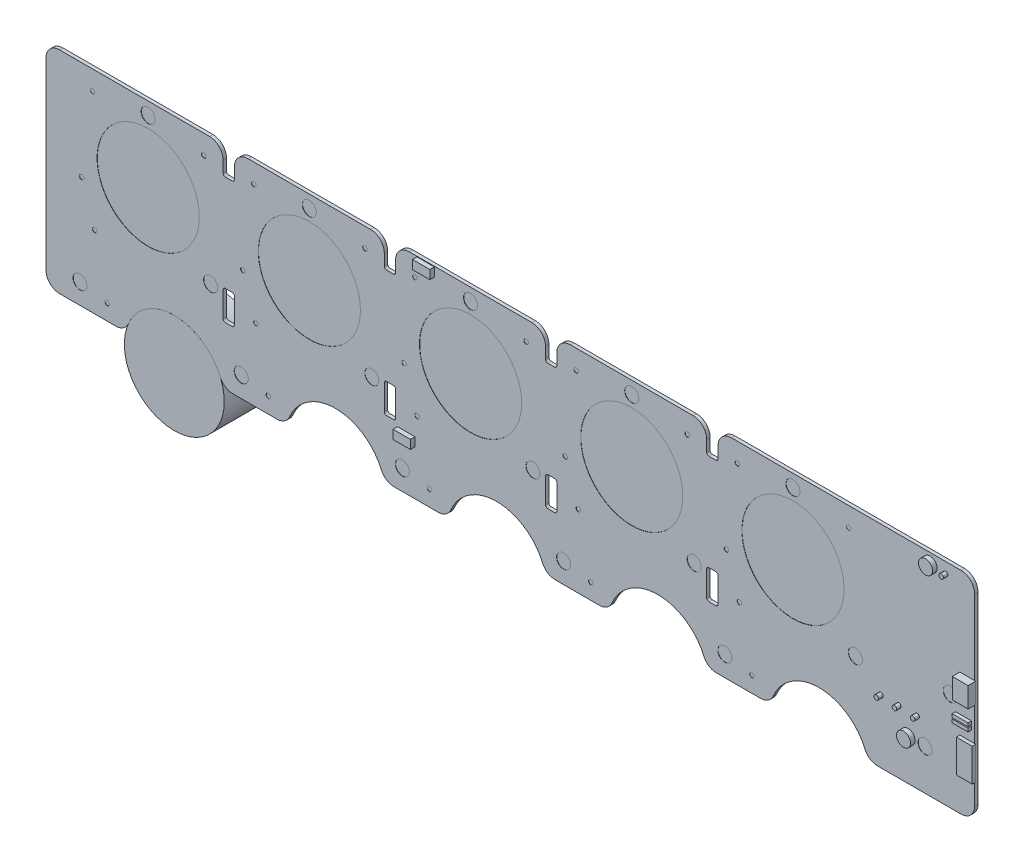
SolidWorks part; units mm, degrees
ref_plane "Plan de face" through (0, 0, 0) normal (0, 0, 1) x (1, 0, 0)
ref_plane "Plan de dessus" through (0, 0, 0) normal (0, 1, 0) x (1, 0, 0)
ref_plane "Plan de droite" through (0, 0, 0) normal (1, 0, 0) x (0, 0, -1)
sketch "Esquisse1" plane through (0, 0, 0) normal (0, 0, 1) x (1, 0, 0)
  line L0 (-142, 0) -> (-71, 0) construction
  line L1 (-187, 33) -> (222, 33)
  line L2 (-187, 33) -> (-187, -60)
  line L3 (-187, -60) -> (222, -60)
  line L4 (222, 33) -> (222, -60)
  line L5 (-71, 0) -> (0, 0) construction
  line L6 (0, 0) -> (71, 0) construction
  line L7 (71, 0) -> (142, 0) construction
  line L8 (-142, 0) -> (-187, 0) construction
  line L9 (142, 0) -> (222, 0) construction
  circle A0 centre (-142, 0) radius 22.5
  circle A1 centre (-71, 0) radius 22.5
  circle A2 centre (0, 0) radius 22.5
  circle A3 centre (71, 0) radius 22.5
  circle A4 centre (142, 0) radius 22.5
  dimension "D1" = 71
  dimension "D2" = 45
  dimension "D3" = 45
  dimension "D4" = 33
  dimension "D5" = 60
  dimension "D6" = 80
  dimension "D7" = 409
extrude "PCB_rectangulaire" add sketch "Esquisse1" against normal blind 1.5 contours L1 L4 L3 L2
extrude "position_trou" cut sketch "Esquisse1<3>" against normal blind 0.1 contours A0 | A1 | A2 | A3 | A4 region at (-142, 0, 0) region at (-71, 0, 0) region at (0, 0, 0) region at (71, 0, 0)
sketch "Esquisse1<3>" plane through (0, 0, 0) normal (0, 0, 1) x (1, 0, 0) same geometry as "Esquisse1"
sketch "Esquisse3" plane through (0, 0, 0) normal (0, 0, 1) x (1, 0, 0)
  line L0 (-187, 33) -> (222, 33) construction
  line L1 (-109, 33) -> (-104, 33)
  line L2 (-109, 33) -> (-109, 22)
  line L3 (-108, 21) -> (-105, 21)
  line L4 (-104, 33) -> (-104, 22)
  line L5 (-106.5, 21) -> (-106.5, 0) construction
  line L6 (-108, -21.5) -> (-105, -21.5)
  line L7 (-109, -22.5) -> (-109, -33.5)
  line L8 (-108, -34.5) -> (-105, -34.5)
  line L9 (-104, -22.5) -> (-104, -33.5)
  line L10 (-106.5, 0) -> (-106.5, -21.5) construction
  line L11 (-142, 0) -> (-71, 0) construction
  arc A0 (-105, 21) -> (-104, 22) centre (-105, 22) ccw
  arc A1 (-109, 22) -> (-108, 21) centre (-108, 22) ccw
  arc A2 (-105, -34.5) -> (-104, -33.5) centre (-105, -33.5) ccw
  arc A3 (-109, -33.5) -> (-108, -34.5) centre (-108, -33.5) ccw
  arc A4 (-105, -21.5) -> (-104, -22.5) centre (-105, -22.5) cw
  arc A5 (-108, -21.5) -> (-109, -22.5) centre (-108, -22.5) ccw
  point P17 (-104, -28)
  point P20 (-104, 21)
  point P25 (-104, -34.5)
  point P28 (-109, -34.5)
  point P31 (-104, -21.5)
  dimension "D5" = 1
  dimension "D1" = 5
  dimension "D2" = 12
  dimension "D3" = 13
  dimension "D4" = 28
extrude "passage_appui_flanc et passage jeton" cut sketch "Esquisse3" against normal through all
pattern_linear "Répétition linéaire1" count 4 spacing 71 along (1, 0, 0) of "passage_appui_flanc et passage jeton"
sketch "Esquisse2" plane through (0, 0, 0) normal (0, 0, 1) x (1, 0, 0)
  line L6 (-166.4921, 24.4921) -> (-164.9365, 22.9365) construction
  line L7 (-117.5079, 24.4921) -> (-119.0635, 22.9365) construction
  line L8 (-166.4921, 24.4921) -> (-117.5079, 24.4921) construction
  circle A0 centre (-171.2929, -10.7071) radius 1
  circle A1 centre (-165.5494, -28) radius 1
  circle A2 centre (-160.0562, -53.0562) radius 1
  circle A3 centre (-166.4921, 24.4921) radius 1
  circle A4 centre (-117.5079, 24.4921) radius 1
  circle A5 centre (-172, -51) radius 3.1
  circle A6 centre (-114.5, -23) radius 3.1
  circle A7 centre (-142, 27.5) radius 3.1
  circle A8 centre (211.2924, -16.5875) radius 3.1
  circle A9 centre (200.1924, -42.0875) radius 3.1
  dimension "D1" = 2
  dimension "D2" = 6.2
  dimension "D3" = 2.2
extrude "position_capteur-LED" cut sketch "Esquisse2" against normal blind 0.1
sketch "Esquisse4" plane through (0, 0, 0) normal (0, 0, 1) x (1, 0, 0)
  line L0 (-130.5, -65) -> (-59.5, -65) construction
  line L1 (-59.5, -65) -> (11.5, -65) construction
  line L2 (11.5, -65) -> (82.5, -65) construction
  line L3 (82.5, -65) -> (153.5, -65) construction
  line L4 (-142, 0) -> (-71, 0) construction
  circle A0 centre (-130.5, -65) radius 22
  circle A1 centre (-59.5, -65) radius 22 construction
  circle A2 centre (11.5, -65) radius 22 construction
  circle A3 centre (82.5, -65) radius 22 construction
  circle A4 centre (153.5, -65) radius 22 construction
  dimension "D1" = 44
  dimension "D2" = 11.5
  dimension "D3" = 65
extrude "echappement" cut sketch "Esquisse4" against normal through all
pattern_linear "Répétition linéaire3" count 5 spacing 71 along (1, 0, 0) of "position_capteur-LED", "echappement"
fillet "Congé1" radius 6 22 edges at (-187, -60, -0.75) (-187, 33, -0.75) (-109, 33, -0.75) (-104, 33, -0.75) (-38, 33, -0.75) (-33, 33, -0.75) (33, 33, -0.75) (38, 33, -0.75) (104, 33, -0.75) (109, 33, -0.75) (222, 33, -0.75) (222, -60, -0.75) (-109.0757, -60, -0.75) (-151.9243, -60, -0.75) (174.9243, -60, -0.75) (132.0757, -60, -0.75) (103.9243, -60, -0.75) (61.0757, -60, -0.75) (32.9243, -60, -0.75) (-9.9243, -60, -0.75) (-38.0757, -60, -0.75) (-80.9243, -60, -0.75)
sketch "Esquisse5" plane through (0, 0, 0) normal (0, 0, 1) x (1, 0, 0)
  line L0 (180.6924, -32.1875) -> (188.6924, -32.1875) construction
  line L1 (188.6924, -32.1875) -> (196.6924, -32.1875) construction
  line L3 (-23.6286, 32.7521) -> (-15.9214, 32.7521)
  line L4 (-23.6286, 32.7521) -> (-23.6286, 28.863)
  line L5 (-23.6286, 28.863) -> (-15.9214, 28.863)
  line L6 (-15.9214, 32.7521) -> (-15.9214, 28.863)
  line L7 (-32.1757, -36.2979) -> (-24.4686, -36.2979)
  line L8 (-32.1757, -36.2979) -> (-32.1757, -40.187)
  line L9 (-32.1757, -40.187) -> (-24.4686, -40.187)
  line L10 (-24.4686, -36.2979) -> (-24.4686, -40.187)
  line L11 (-28.3221, -36.5979) -> (-28.3221, -36.2979) construction
  line L13 (-24.7686, -38.2425) -> (-24.4686, -38.2425) construction
  line L15 (-19.775, 32.4521) -> (-19.775, 32.7521) construction
  line L17 (-16.2214, 30.8076) -> (-15.9214, 30.8076) construction
  circle A0 centre (180.6924, -32.1875) radius 1
  circle A1 centre (188.6924, -32.1875) radius 1
  circle A2 centre (196.6924, -32.1875) radius 1
  circle A3 centre (209.2395, 28.2642) radius 1
  circle A8 centre (192.6924, -42.0875) radius 3.1
  circle A9 centre (202.3924, 28.5125) radius 3.1
  dimension "D1" = 2
  dimension "D2" = 6.2
  dimension "D3" = 0.3
extrude "bouton et IR" add sketch "Esquisse5" along normal blind 2
sketch "Esquisse6" plane through (222, 0, 0) normal (1, 0, 0) x (0, 0, -1)
  line L1 (-3.335, -6.0675) -> (0, -6.0675)
  line L2 (-3.335, -6.0675) -> (-3.335, -15.0075)
  line L3 (-3.335, -15.0075) -> (0, -15.0075)
  line L4 (0, -6.0675) -> (0, -15.0075)
  line L5 (-1.535, -30.1124) -> (0, -30.1124)
  line L6 (-1.535, -30.1124) -> (-1.535, -44.5624)
  line L7 (-1.535, -44.5624) -> (0, -44.5624)
  line L8 (0, -30.1124) -> (0, -44.5624)
  line L9 (-3.4, -22.2375) -> (-1.9, -22.2375)
  line L10 (-3.4, -22.2375) -> (-3.4, -23.7375)
  line L11 (-3.4, -23.7375) -> (-1.9, -23.7375)
  line L12 (-1.9, -22.2375) -> (-1.9, -23.7375)
  line L19 (0, 27) -> (0, -54) construction
  line L20 (-1.9, -21.7375) -> (-1.9, -22.2375) construction
  line L21 (-3.4, -20.2375) -> (-1.9, -20.2375)
  line L22 (-3.4, -20.2375) -> (-3.4, -21.7375)
  line L23 (-3.4, -21.7375) -> (-1.9, -21.7375)
  line L24 (-1.9, -20.2375) -> (-1.9, -21.7375)
  point P12 (-3.4, -20.9875)
  point P22 (-3.4, -22.9875)
  dimension "D1" = 6.4
  dimension "D2" = 1.5
  dimension "D3" = 2
  dimension "D4" = 3.4
extrude "cote_droit" add sketch "Esquisse6" against normal blind 7 from offset 0.5
extrude "degagement_jeton" add sketch "Esquisse4<2>" against normal blind 20 separate body contours A0
sketch "Esquisse4<2>" plane through (0, 0, 0) normal (0, 0, 1) x (1, 0, 0) same geometry as "Esquisse4"
sketch "repère_batterie" plane through (222, 0, 0) normal (1, 0, 0) x (0, 0, -1)
  line L0 (1.5, 27) -> (1.5, -54) construction
  line L1 (1.5, -43.8875) -> (5, -43.8875)
  line L2 (1.5, -43.8875) -> (1.5, -49.8875)
  line L3 (1.5, -49.8875) -> (5, -49.8875)
  line L4 (5, -43.8875) -> (5, -49.8875)
  line L9 (5.5, -43.8875) -> (5.5, -49.8875)
  line L10 (6.9, -43.8875) -> (6.9, -49.8875) construction
  line L11 (5, -49.8875) -> (5.5, -49.8875) construction
  line L12 (5.5, -49.8875) -> (6.9, -49.8875) construction
  line L13 (5, -43.8875) -> (5.5, -43.8875) construction
  line L14 (5.5, -43.8875) -> (6.9, -43.8875) construction
  line L15 (5, -43.6375) -> (54.5, -43.6375) construction
  line L16 (5, -21.6375) -> (54.5, -21.6375)
  line L17 (5, -21.6375) -> (5, -54.6375)
  line L18 (5, -54.6375) -> (54.5, -54.6375)
  line L19 (54.5, -21.6375) -> (54.5, -54.6375)
  line L20 (5, -43.3875) -> (5, -43.8875) construction
  line L21 (1.5, -37.3875) -> (5, -37.3875)
  line L22 (1.5, -37.3875) -> (1.5, -43.3875)
  line L23 (1.5, -43.3875) -> (5, -43.3875)
  line L24 (5, -37.3875) -> (5, -43.3875)
  line L25 (6, -48.1375) -> (6, -43.6375) construction
  line L26 (1.5, -60) -> (0, -60) construction
  line L27 (6, -43.6375) -> (6, -39.1375) construction
  point P14 (5, -46.8875)
  point P21 (5, -43.6375)
  dimension "D1" = 33
  dimension "D2" = 49.5
  dimension "D3" = 11
  dimension "D4" = 3.5
  dimension "D5" = 5.4
  dimension "D6" = 6
  dimension "D7" = 3.25
  dimension "D8" = 13.1125
  dimension "D9" = 5.3625
  dimension "D10" = 0.5
  dimension "D11" = 9
  dimension "D12" = 1
